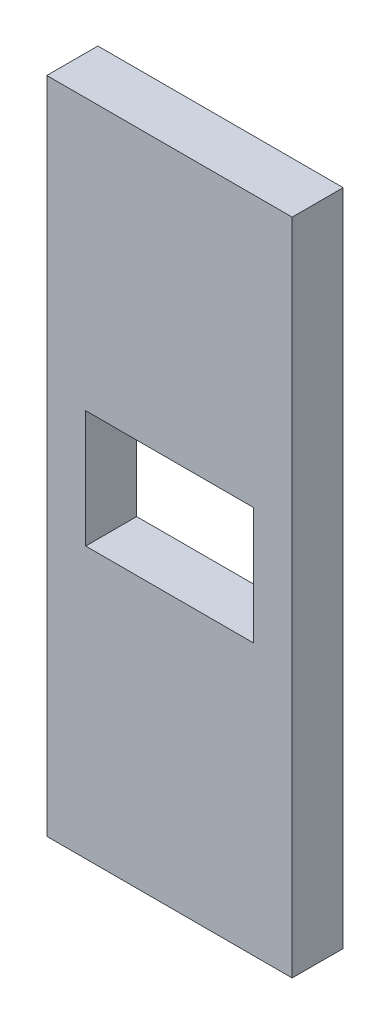
SolidWorks part; units mm, degrees
ref_plane "Front Plane" through (0, 0, 0) normal (0, 0, 1) x (1, 0, 0)
ref_plane "Top Plane" through (0, 0, 0) normal (0, 1, 0) x (1, 0, 0)
ref_plane "Right Plane" through (0, 0, 0) normal (1, 0, 0) x (0, 0, -1)
sketch "Sketch1" plane through (0, 0, 0) normal (0, 0, 1) x (1, 0, 0)
  line L0 (0, 67.15) -> (0, 44.75)
  line L1 (0, 67.15) -> (25, 67.15)
  line L2 (0, 44.75) -> (0, 39.55)
  line L3 (25, 0) -> (0, 0)
  line L4 (3.96, 39.55) -> (21.04, 39.55)
  line L5 (3.96, 27.6) -> (21.04, 27.6)
  line L6 (3.96, 39.55) -> (3.96, 27.6)
  line L7 (21.04, 39.55) -> (21.04, 27.6)
  line L8 (0, 44.75) -> (25, 44.75) construction
  line L9 (0, 39.55) -> (25, 39.55) construction
  line L10 (0, 39.55) -> (0, 27.6)
  line L11 (0, 27.6) -> (0, 22.4)
  line L12 (25, 44.75) -> (25, 39.55)
  line L13 (25, 67.15) -> (25, 44.75)
  line L14 (0, 22.4) -> (0, 0)
  line L15 (25, 39.55) -> (25, 27.6)
  line L16 (25, 27.6) -> (25, 22.4)
  line L17 (25, 22.4) -> (25, 0)
  line L18 (0, 27.6) -> (25, 27.6) construction
  line L19 (25, 22.4) -> (0, 22.4) construction
  line L20 (12.5, -0.0005) -> (12.5, 4.0956) construction
  point P18 (12.5, 27.6)
  point P20 (12.5, 39.55)
  point P21 (12.5, 67.15)
  dimension "D1" = 22.4
  dimension "D2" = 11.95
  dimension "D3" = 5.2
  dimension "D4" = 25
  dimension "D5" = 11.95
  dimension "D6" = 17.08
extrude "Boss-Extrude1" add sketch "Sketch1" along normal blind 5.2
